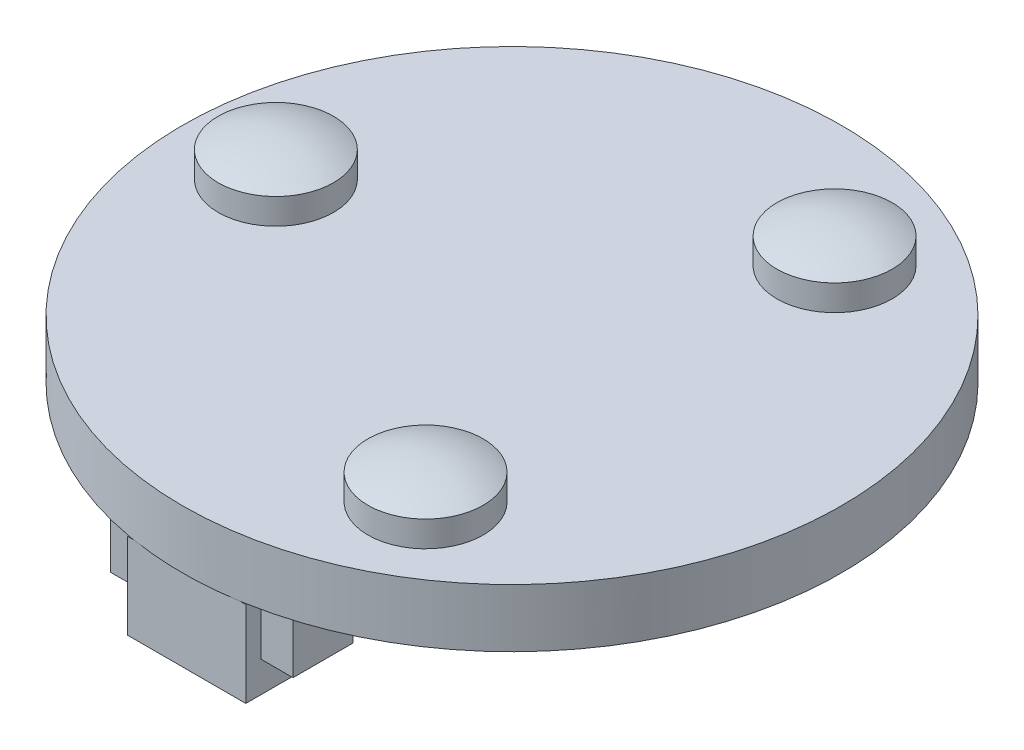
SolidWorks part; units mm, degrees
ref_plane "Front Plane" through (0, 0, 0) normal (0, 0, 1) x (1, 0, 0)
ref_plane "Top Plane" through (0, 0, 0) normal (0, 1, 0) x (1, 0, 0)
ref_plane "Right Plane" through (0, 0, 0) normal (1, 0, 0) x (0, 0, -1)
sketch "Sketch1" plane through (0, 0, 0) normal (0, 1, 0) x (1, 0, 0)
  circle A0 centre (0, 0) radius 15.35
  dimension "D1" = 30.7
extrude "Boss-Extrude1" add sketch "Sketch1" along normal blind 2.71
sketch "Sketch2" plane through (0, 2.71, 0) normal (0, 1, 0) x (-1, 0, 0)
  line L1 (-5.5, 9.5263) -> (0, 0) construction
  line L2 (0, 3.3605) -> (0, -3.3605) construction
  circle A0 centre (-5.5, 9.5263) radius 2.685
  dimension "D1" = 5.37
  dimension "D2" = 11
  dimension "D3" = 30
extrude "Boss-Extrude2" add sketch "Sketch2" along normal blind 1.2
dome "Dome1" faces to dome 1 distance 0.6 reverse direction no elliptical dome no face at (5.5, 3.91, 12.2113) parameters "D1"=0.6
pattern_circular "CirPattern1" count 3 over 360 about axis through (0, 2.71, 0) along (0, 1, 0) of "Dome1", "Boss-Extrude2"
sketch "Sketch3" plane through (0, 0, 0) normal (0, -1, 0) x (1, 0, 0)
  line L0 (0, 15.35) -> (0, -15.35) construction
  line L2 (2.75, 15.15) -> (-2.75, 15.15)
  line L3 (2.75, 15.15) -> (2.75, 10.95)
  line L4 (2.75, 10.95) -> (-2.75, 10.95)
  line L5 (-2.75, 15.15) -> (-2.75, 10.95)
  line L6 (2.75, 15.15) -> (-2.75, 10.95) construction
  line L7 (2.75, 10.95) -> (-2.75, 15.15) construction
  line L8 (-2.75, 13.05) -> (4.4429, 13.05) construction
  line L9 (2.75, 14.45) -> (4.25, 14.45)
  line L10 (4.25, 14.45) -> (4.25, 11.65)
  line L11 (4.25, 11.65) -> (2.75, 11.65)
  line L12 (-4.25, 11.65) -> (-2.75, 11.65)
  line L13 (-4.25, 14.45) -> (-4.25, 11.65)
  line L14 (-2.75, 14.45) -> (-4.25, 14.45)
  line L15 (0, 0) -> (-15.35, 0) construction
  line L16 (2.75, -14.45) -> (4.25, -14.45)
  line L17 (4.25, -14.45) -> (4.25, -11.65)
  line L18 (4.25, -11.65) -> (2.75, -11.65)
  line L19 (2.75, -15.15) -> (2.75, -10.95)
  line L20 (2.75, -10.95) -> (-2.75, -10.95)
  line L21 (-4.25, -11.65) -> (-2.75, -11.65)
  line L22 (-4.25, -14.45) -> (-4.25, -11.65)
  line L23 (-2.75, -14.45) -> (-4.25, -14.45)
  line L24 (-2.75, -15.15) -> (-2.75, -10.95)
  line L25 (2.75, -15.15) -> (-2.75, -15.15)
  line L26 (-1.5955, 10.95) -> (-1.5955, 0) construction
  line L27 (-1.5955, 0) -> (-1.5955, -10.95) construction
  point P4 (0, 13.05)
  point P16 (4.25, 13.05)
  circle M1 centre (0, 0) radius 15.35
  dimension "D1" = 5.5
  dimension "D3" = 4.2
  dimension "D4" = 2.8
  dimension "D5" = 1.5
  dimension "D6" = 21.9
extrude "Boss-Extrude3" add sketch "Sketch3" along normal blind 2.55 contours L2 L5 L4 L3 | L25 L19 L20 L24 | L11 L10 L9 L3 | L5 L14 L13 L12 | L19 L16 L17 L18 | L23 L24 L21 L22 | L3 L2 M1 | L2 L5 M1 | L25 L24 M1 | L25 L19 M1 region at (2.6575, 0, 15.134) region at (0, 0, 13.0488) region at (-2.6575, 0, 15.134) region at (3.5, 0, 13.05) region at (0, 0, -13.0488) region at (2.6575, 0, -15.134) region at (-3.5, 0, 13.05) region at (-2.6575, 0, -15.134) region at (3.5, 0, -13.05) region at (-3.5, 0, -13.05)
sketch "Sketch4" plane through (0, -2.55, 0) normal (0, -1, 0) x (1, 0, 0)
  line L0 (2.75, 10.95) -> (-2.75, 10.95) construction
  line L1 (2.75, 15.15) -> (-2.75, 15.15) construction
  line L2 (2.75, 10.95) -> (-2.75, 10.95)
  line L3 (2.75, 15.15) -> (-2.75, 15.15)
  line L4 (2.75, 15.15) -> (2.75, 10.95)
  line L5 (-2.75, 10.95) -> (-2.75, 15.15)
  line L6 (2.75, -15.15) -> (2.75, -10.95)
  line L7 (2.75, -10.95) -> (-2.75, -10.95)
  line L8 (-2.75, -10.95) -> (-2.75, -15.15)
  line L9 (-2.75, -15.15) -> (2.75, -15.15)
  line L10 (2.75, -15.15) -> (2.7698, -15.1661)
  line M2 (-2.75, 15.15) -> (-2.75, 14.45)
  line M6 (-2.75, 11.65) -> (-2.75, 10.95)
  line M7 (-2.75, 10.95) -> (2.75, 10.95)
  line M8 (2.75, 10.95) -> (2.75, 11.65)
  line M12 (2.75, 14.45) -> (2.75, 15.15)
  line M14 (2.75, 15.15) -> (-2.75, 15.15)
extrude "Boss-Extrude4" add sketch "Sketch4" along normal blind 1.44 contours L5 L4 M6 M7 M8 M12 M14 M2 | L8 L9 L6 L7 region at (0, -2.55, 13.05) region at (0, -2.55, -13.05)
sketch "Sketch5" plane through (0, 0, 0) normal (0, -1, 0) x (1, 0, 0)
  line L0 (-5.1644, -9.426) -> (-2.0166, -2.879)
  line L1 (-2.0166, -2.879) -> (-8.0142, 0.0047)
  line L2 (-8.0142, 0.0047) -> (-11.162, -6.5423)
  line L3 (-11.162, -6.5423) -> (-5.1644, -9.426)
  line L4 (-4.25, -14.45) -> (-4.25, -11.65) construction
  line L5 (-5.1644, -9.426) -> (-5.1644, -14.4552) construction
  line L8 (-2.0166, -2.879) -> (15.0776, -2.879) construction
  arc A0 (-2.75, 15.1017) -> (-2.75, -15.1017) centre (0, 0) ccw construction
  arc A1 (2.75, -15.1017) -> (2.75, 15.1017) centre (0, 0) ccw construction
  dimension "D1" = 6.6548
  dimension "D2" = 7.2644
  dimension "D3" = 5.0292
  dimension "D4" = 0.9144
  dimension "D5" = 17.0942
extrude "Chip" add sketch "Sketch5" along normal blind 1.7018
ref_point "Centerpoint"
move or copy body "Body-Move/Copy1" [suppressed] bodies to move or copy 106
